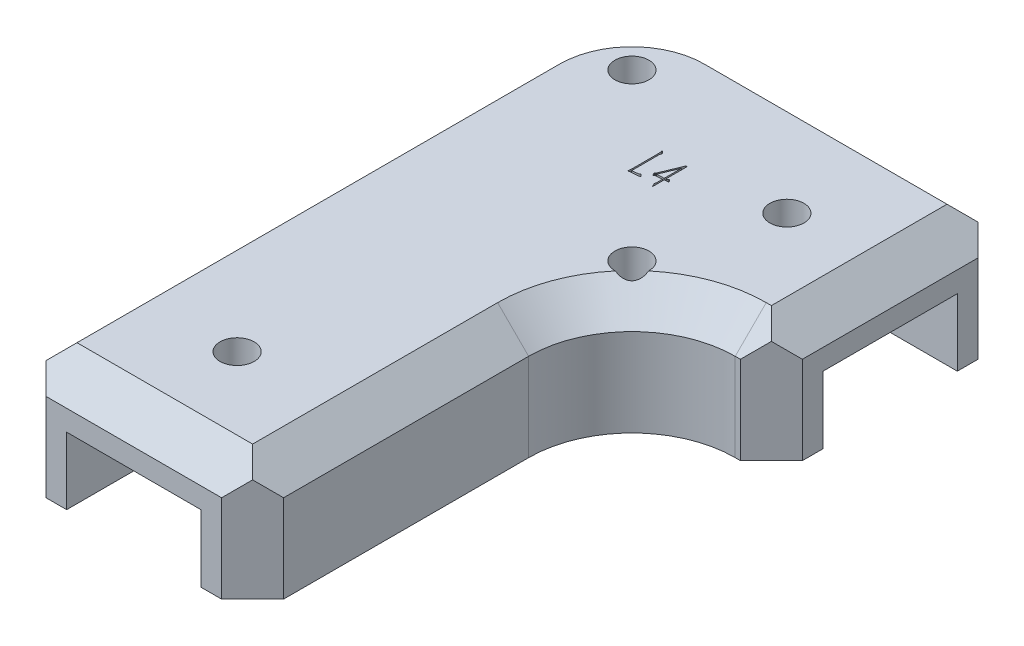
SolidWorks part; units mm, degrees
ref_plane "前视基准面" through (0, 0, 0) normal (0, 0, 1) x (1, 0, 0)
ref_plane "上视基准面" through (0, 0, 0) normal (0, 1, 0) x (1, 0, 0)
ref_plane "右视基准面" through (0, 0, 0) normal (1, 0, 0) x (0, 0, -1)
sketch "草图1" plane through (0, 0, 0) normal (0, 0, 1) x (1, 0, 0)
  line L1 (0, 0) -> (13, 0)
  line L2 (0, 0) -> (0, 13)
  line L3 (0, 13) -> (13, 13)
  line L4 (13, 0) -> (13, 13)
  line L5 (-5, 18) -> (18, 18)
  line L6 (-5, 18) -> (-5, -5)
  line L7 (-5, -5) -> (18, -5)
  line L8 (18, 18) -> (18, -5)
  dimension "D1" = 13
  dimension "D2" = 13
  dimension "D3" = 23
  dimension "D4" = 23
  dimension "D5" = 5
  dimension "D6" = 5
extrude "凸台-拉伸1" add sketch "草图1" along normal blind 59.72
sketch "草图2" plane through (0, -5, 0) normal (0, -1, 0) x (1, 0, 0)
  line L0 (-5, 59.72) -> (18, 59.72) construction
  line L1 (-5, 59.72) -> (-5, 0) construction
  circle A0 centre (6.5, 49.72) radius 1.65
  dimension "D1" = 3.3
  dimension "D2" = 10
  dimension "D3" = 11.5
extrude "切除-拉伸1" cut sketch "草图2" against normal blind 34
sketch "草图3" [suppressed] plane through (0, 25, 0) normal (0, 1, 0) x (1, 0, 0)
  line L0 (25, 0) -> (-5, 0) construction
  line L1 (2.5796, -2) -> (18.5796, -2)
  line L2 (2.5796, -2) -> (2.5796, -16)
  line L3 (2.5796, -16) -> (18.5796, -16)
  line L4 (18.5796, -2) -> (18.5796, -16)
  dimension "D1" = 14
  dimension "D2" = 2
  dimension "D3" = 16
sketch "草图4" plane through (18, 0, 0) normal (1, 0, 0) x (0, 0, -1)
  line L0 (-59.72, -5) -> (0, -5) construction
  line L1 (0, 18) -> (-23, 18)
  line L2 (0, 18) -> (0, -5)
  line L3 (0, -5) -> (-23, -5)
  line L4 (-23, 18) -> (-23, -5)
  circle A0 centre (-11.5, 6.5) radius 3
  dimension "D2" = 11.5
  dimension "D3" = 11.5
  dimension "D4" = 6
  dimension "D1" = 23
extrude "凸台-拉伸2" add sketch "草图4" along normal blind 3.5
sketch "草图5" plane through (21.5, 0, 0) normal (1, 0, 0) x (0, 0, -1)
  line L0 (0, -5) -> (0, 18) construction
  line L1 (-5, 0) -> (-18, 0)
  line L2 (-5, 0) -> (-5, 13)
  line L3 (-5, 13) -> (-18, 13)
  line L4 (-18, 0) -> (-18, 13)
  line L5 (-5, 0) -> (-18, 13) construction
  line L6 (-5, 13) -> (-18, 0) construction
  line L7 (-23, -5) -> (0, -5) construction
  point P0 (-11.5, 6.5)
  dimension "D1" = 13
  dimension "D2" = 13
  dimension "D3" = 5
  dimension "D4" = 5
extrude "拉伸-薄壁1" add sketch "草图5" along normal blind 10 thin thin type one direction wall 5
sketch "草图6" plane through (0, 18, 0) normal (0, 1, 0) x (1, 0, 0)
  line L0 (31.5, 0) -> (31.5, -23) construction
  line L1 (31.5, 0) -> (-5, 0) construction
  circle A0 centre (21.5, -11.5) radius 1.65
  dimension "D1" = 3.3
  dimension "D2" = 10
  dimension "D3" = 11.5
extrude "切除-拉伸2" cut sketch "草图6" against normal blind 39
sketch "草图7" plane through (21.5, 0, 0) normal (1, 0, 0) x (0, 0, -1)
  line L1 (-18, 13) -> (-5, 13)
  line L2 (-18, 13) -> (-18, 0)
  line L3 (-18, 0) -> (-5, 0)
  line L4 (-5, 13) -> (-5, 0)
extrude "切除-拉伸3" cut sketch "草图7" against normal blind 13
chamfer "倒角1" distance 3 angle 45 1 edges at (13, 6.5, 18)
chamfer "倒角2" [suppressed] distance 3 angle 45
sketch "草图8" plane through (0, -5, 0) normal (0, -1, 0) x (1, 0, 0)
  line L1 (-5, 59.72) -> (31.5, 59.72)
  line L2 (-5, 59.72) -> (-5, 0)
  line L3 (-5, 0) -> (31.5, 0)
  line L4 (31.5, 59.72) -> (31.5, 0)
extrude "切除-拉伸4" cut sketch "草图8" against normal blind 11.5
sketch "草图9" plane through (0, 13, 0) normal (0, -1, 0) x (1, 0, 0)
  line L0 (13, 5) -> (0, 18)
  line L2 (0, 18) -> (0, 0)
  line L3 (0, 0) -> (13, 0)
  line L4 (13, 0) -> (13, 5)
  dimension "D1" = 18
extrude "凸台-拉伸3" add sketch "草图9" along normal blind 6.5
fillet "圆角1" radius 10 1 edges at (-5, 12.25, 0)
fillet "圆角2" radius 10 1 edges at (18, 12.25, 23)
sketch "草图10" plane through (0, 6.5, 0) normal (0, -1, 0) x (1, 0, 0)
  line L0 (-5, 59.72) -> (-5, 10) construction
  line L1 (5, 0) -> (31.5, 0) construction
  line L2 (31.5, 18) -> (16, 18) construction
  line L3 (13, 21) -> (13, 59.72) construction
  circle A0 centre (2, 7) radius 1.65
  circle A1 centre (18, 23) radius 1.65
  dimension "D1" = 7
  dimension "D2" = 7
  dimension "D3" = 3.3
  dimension "D4" = 5
  dimension "D5" = 5
  dimension "D6" = 3.3
extrude "切除-拉伸5" cut sketch "草图10" against normal blind 28.5
chamfer "倒角3" distance 3 angle 45 6 edges at (18, 18, 46.36) (29.75, 18, 23) (20.9289, 18, 25.9289) (18.25, 18, 0) (-2.0711, 18, 2.9289) (-5, 18, 34.86)
chamfer "倒角4" distance 3 angle 45 2 edges at (31.5, 18, 11.5) (6.5, 18, 59.72)
chamfer "倒角5" distance 3 angle 45 4 edges at (31.5, 10.75, 0) (31.5, 10.75, 23) (18, 10.75, 59.72) (-5, 10.75, 59.72)
sketch "草图11" plane through (0, 18, 0) normal (0, 1, 0) x (1, 0, 0)
  text T0 "L4"
extrude "切除-拉伸6" cut sketch "草图11" against normal blind 0.3
